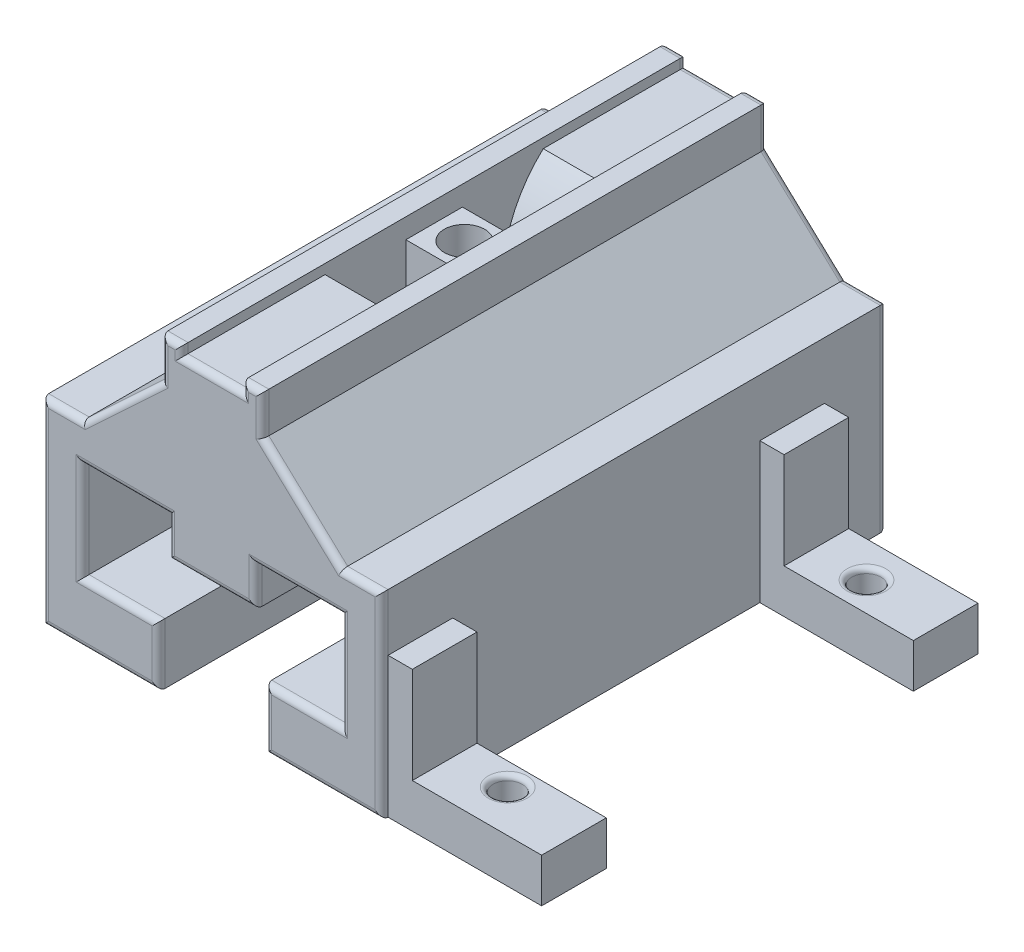
SolidWorks part; units mm, degrees
ref_plane "Front" through (0, 0, 0) normal (0, 0, 1) x (1, 0, 0)
ref_plane "Top" through (0, 0, 0) normal (0, 1, 0) x (1, 0, 0)
ref_plane "Right" through (0, 0, 0) normal (1, 0, 0) x (0, 0, -1)
sketch "Sketch2" plane through (0, 0, 0) normal (0, 0, 1) x (1, 0, 0)
  line L0 (-4.191, 2.6476) -> (-10.16, 2.6476)
  line L1 (-10.16, 2.6476) -> (-10.16, 10.3311)
  line L2 (-10.16, 10.3311) -> (-3.429, 10.3311)
  line L3 (-3.429, 10.3311) -> (-3.429, 7.2831)
  line L4 (-3.429, 7.2831) -> (3.429, 7.2831)
  line L5 (0, -13.7255) -> (0, 13.7255) construction
  line L6 (-4.191, 2.6476) -> (-4.191, -2.1149)
  line L7 (-4.191, -2.1149) -> (-13.335, -2.1149)
  line L8 (-13.335, -2.1149) -> (-13.335, 13.3791)
  line L9 (-13.335, 13.3791) -> (-10.16, 13.3791)
  line L10 (-10.16, 13.3791) -> (-3.9687, 19.1576)
  line L11 (-3.9687, 19.1576) -> (-3.9688, 22.3326)
  line L12 (-3.9688, 22.3326) -> (-2.3813, 22.3326)
  line L13 (-2.3813, 22.3326) -> (-2.3813, 21.5706)
  line L14 (-2.3813, 21.5706) -> (2.3813, 21.5706)
  line L15 (2.3813, 22.3326) -> (2.3813, 21.5706)
  line L16 (3.9688, 22.3326) -> (2.3813, 22.3326)
  line L17 (3.9687, 19.1576) -> (3.9688, 22.3326)
  line L18 (10.16, 13.3791) -> (3.9687, 19.1576)
  line L19 (13.335, 13.3791) -> (10.16, 13.3791)
  line L20 (13.335, -2.1149) -> (13.335, 13.3791)
  line L21 (4.191, -2.1149) -> (13.335, -2.1149)
  line L22 (4.191, 2.6476) -> (4.191, -2.1149)
  line L23 (3.429, 10.3311) -> (3.429, 7.2831)
  line L24 (10.16, 10.3311) -> (3.429, 10.3311)
  line L25 (10.16, 2.6476) -> (10.16, 10.3311)
  line L26 (4.191, 2.6476) -> (10.16, 2.6476)
  point P23 (0, 21.5706)
  point P32 (0, 7.2831)
  dimension "D1" = 4.7625
  dimension "D2" = 9.144
  dimension "D3" = 3.175
  dimension "D4" = 15.494
  dimension "D5" = 3.048
  dimension "D6" = 3.048
  dimension "D7" = 14.2875
  dimension "D8" = 3.175
  dimension "D9" = 0.762
  dimension "D10" = 1.5875
  dimension "D11" = 2.3813
  dimension "D12" = 3.175
  dimension "D13" = 6.731
  dimension "D14" = 3.429
extrude "Boss-Extrude1" add sketch "Sketch2" along normal blind 39.6875
sketch "Sketch3" plane through (0, 21.5706, 0) normal (0, 1, 0) x (1, 0, 0)
  line L0 (0, 0) -> (0, -39.6875) construction
  line L1 (-13.335, -19.8438) -> (13.335, -19.8438) construction
  line L2 (-13.335, -39.6875) -> (-13.335, 0) construction
  line L3 (13.335, -39.6875) -> (13.335, 0) construction
  line L4 (2.3813, 0) -> (-2.3813, 0)
  line L5 (-2.3813, 0) -> (-2.3813, -39.6875)
  line L6 (-2.3813, -39.6875) -> (2.3813, -39.6875)
  line L7 (2.3813, -39.6875) -> (2.3813, 0)
  line L8 (2.3813, 0) -> (-2.3813, 0)
  line L9 (-2.3813, 0) -> (-2.3813, -39.6875)
  line L10 (-2.3813, -39.6875) -> (2.3813, -39.6875)
  line L11 (2.3813, -39.6875) -> (2.3813, 0)
  circle A0 centre (0, -19.8437) radius 1.5875
  dimension "D2" = 3.175
  dimension "D1" = 0
extrude "Cut-Extrude1" cut sketch "Sketch3" against normal blind 39.6875 contours A0 region at (0, 21.5706, 19.8437)
sketch "Sketch4" plane through (0, 7.2831, 0) normal (0, -1, 0) x (1, 0, 0)
  line L1 (0.9165, 18.2562) -> (1.8331, 19.8437)
  line L2 (1.8331, 19.8437) -> (0.9165, 21.4312)
  line L3 (0.9165, 21.4312) -> (-0.9165, 21.4312)
  line L4 (-3.429, 0) -> (3.429, 0)
  line L5 (3.429, 0) -> (3.429, 39.6875)
  line L6 (3.429, 39.6875) -> (-3.429, 39.6875)
  line L7 (-3.429, 39.6875) -> (-3.429, 0)
  line L8 (-3.429, 0) -> (3.429, 0)
  line L9 (3.429, 0) -> (3.429, 39.6875)
  line L10 (3.429, 39.6875) -> (-3.429, 39.6875)
  line L11 (-3.429, 39.6875) -> (-3.429, 0)
  line L12 (-0.9165, 21.4312) -> (-1.8331, 19.8437)
  line L13 (-1.8331, 19.8437) -> (-0.9165, 18.2562)
  line L14 (-0.9165, 18.2562) -> (0.9165, 18.2562)
  circle A0 centre (0, 19.8437) radius 1.5875 construction
  circle M11 centre (0, 19.8437) radius 1.5875
  dimension "D2" = 3.175
  dimension "D1" = 0
extrude "Cut-Extrude3" cut sketch "Sketch4" against normal blind 5 contours M11 | L12 L13 M11 | L13 L14 M11 | L14 L1 M11 | L1 L2 M11 | L2 L3 M11 | L3 L12 M11 region at (0.8204, 7.2831, 18.4228) region at (1.6408, 7.2831, 19.8437) region at (0, 7.2831, 19.8437) region at (-0.8204, 7.2831, 18.4228) region at (-1.6408, 7.2831, 19.8437) region at (0.8204, 7.2831, 21.2647) region at (-0.8204, 7.2831, 21.2647)
sketch "Sketch5" plane through (2.3813, 0, 0) normal (-1, 0, 0) x (0, 0, 1)
  line L3 (11.2713, 21.5706) -> (17.6212, 21.5706)
  line L6 (28.4163, 21.5706) -> (22.0663, 21.5706)
  line L7 (28.1707, 7.2831) -> (20.7963, 7.2831)
  line L8 (22.0663, 10.3311) -> (17.6212, 10.3311)
  line L9 (19.8438, 21.5706) -> (19.8438, 7.2831) construction
  line L12 (11.5168, 7.2831) -> (17.6213, 7.2831)
  line L16 (20.7963, 7.2831) -> (17.6213, 7.2831)
  line L19 (22.0663, 20.7705) -> (17.6212, 20.7705)
  line L21 (17.6212, 20.7705) -> (17.6212, 10.3311)
  line L22 (22.0663, 20.7705) -> (22.0663, 10.3311)
  line L24 (17.6212, 21.5706) -> (22.0663, 21.5706)
  arc A0 (28.4163, 21.5706) -> (28.1707, 7.2831) centre (35.1321, 14.3093) ccw
  arc A1 (11.2713, 21.5706) -> (11.5168, 7.2831) centre (4.5554, 14.3093) cw
  dimension "D1" = 4.445
extrude "Cut-Extrude5" cut sketch "Sketch5" along normal up to surface (4.7625 mm away) up to face at (-2.3813, 21.9516, 19.8438)
sketch "Sketch6" plane through (-2.3813, 0, 0) normal (1, 0, 0) x (0, 0, -1)
  line L0 (-26.0766, 10.3311) -> (-13.6109, 10.3311)
  line L1 (-11.5168, 7.2831) -> (-28.1707, 7.2831)
  line L6 (0, 21.5706) -> (0, 22.3326)
  line L7 (0, 22.3326) -> (-39.6875, 22.3326)
  line L8 (-39.6875, 22.3326) -> (-39.6875, 21.5706)
  line L9 (-39.6875, 21.5706) -> (-28.4163, 21.5706)
  line L10 (-28.1707, 7.2831) -> (-11.5168, 7.2831)
  line L11 (-11.2713, 21.5706) -> (0, 21.5706)
  arc A2 (-28.1707, 7.2831) -> (-28.4163, 21.5706) centre (-35.1321, 14.3093) ccw
  arc A3 (-11.2713, 21.5706) -> (-11.5168, 7.2831) centre (-4.5554, 14.3093) ccw
  arc A4 (-28.1707, 7.2831) -> (-26.0766, 10.3311) centre (-35.1321, 14.3093) ccw
  arc A5 (-13.6109, 10.3311) -> (-11.5168, 7.2831) centre (-4.5554, 14.3093) ccw
  dimension "D1" = 0
extrude "Cut-Extrude6" cut sketch "Sketch6" against normal blind 3.175 and the other way blind 8.255 contours L1 A4 L0 A5
fillet "Fillet1" radius 0.508 52 edges at (-7.1755, 2.6476, 0) (-10.16, 6.4894, 0) (-6.7945, 10.3311, 0) (-3.429, 8.8071, 0) (0, 7.2831, 0) (3.429, 8.8071, 0) (6.7945, 10.3311, 0) (10.16, 6.4894, 0) (7.1755, 2.6476, 0) (4.191, 0.2664, 0) (8.763, -2.1149, 0) (13.335, 5.6321, 0) (11.7475, 13.3791, 0) (7.0644, 16.2684, 0) (3.9688, 20.7451, 0) (3.175, 22.3326, 0) (2.3813, 21.9516, 0) (0, 21.5706, 0) (-2.3813, 21.9516, 0) (-3.175, 22.3326, 0) (-3.9688, 20.7451, 0) (-7.0644, 16.2684, 0) (-11.7475, 13.3791, 0) (-13.335, 5.6321, 0) (-8.763, -2.1149, 0) (-4.191, 0.2664, 0) (-8.763, -2.1149, 39.6875) (-13.335, 5.6321, 39.6875) (-11.7475, 13.3791, 39.6875) (-7.0644, 16.2684, 39.6875) (-3.9688, 20.7451, 39.6875) (-3.175, 22.3326, 39.6875) (-2.3813, 21.9516, 39.6875) (0, 21.5706, 39.6875) (2.3813, 21.9516, 39.6875) (3.175, 22.3326, 39.6875) (3.9688, 20.7451, 39.6875) (7.0644, 16.2684, 39.6875) (11.7475, 13.3791, 39.6875) (13.335, 5.6321, 39.6875) (8.763, -2.1149, 39.6875) (4.191, 0.2664, 39.6875) (7.1755, 2.6476, 39.6875) (10.16, 6.4894, 39.6875) (6.7945, 10.3311, 39.6875) (3.429, 8.8071, 39.6875) (0, 7.2831, 39.6875) (-3.429, 8.8071, 39.6875) (-6.7945, 10.3311, 39.6875) (-10.16, 6.4894, 39.6875) (-7.1755, 2.6476, 39.6875) (-4.191, 0.2664, 39.6875)
sketch "Sketch7" plane through (13.335, 0, 0) normal (1, 0, 0) x (0, 0, -1)
  line L0 (-39.1795, -2.1149) -> (-0.508, -2.1149) construction
  line L1 (-39.1795, -2.1149) -> (-34.0995, -2.1149)
  line L2 (-39.1795, -2.1149) -> (-39.1795, 8.9054)
  line L3 (-39.1795, 8.9054) -> (-34.0995, 8.9054)
  line L4 (-34.0995, -2.1149) -> (-34.0995, 8.9054)
  line L5 (-9.9695, -2.1149) -> (-4.8895, -2.1149)
  line L6 (-9.9695, -2.1149) -> (-9.9695, 8.9054)
  line L7 (-9.9695, 8.9054) -> (-4.8895, 8.9054)
  line L8 (-4.8895, -2.1149) -> (-4.8895, 8.9054)
  dimension "D1" = 5.08
  dimension "D2" = 24.13
extrude "Boss-Extrude2" add sketch "Sketch7" along normal blind 1.905
sketch "Sketch8" plane through (15.24, 0, 0) normal (1, 0, 0) x (0, 0, -1)
  line L0 (-39.1795, 1.336) -> (-34.0995, 1.336)
  line L1 (-9.9695, 1.336) -> (-4.8895, 1.336)
  line L4 (-39.1795, 8.9054) -> (-39.1795, -2.1149)
  line L5 (-39.1795, -2.1149) -> (-34.0995, -2.1149)
  line L6 (-34.0995, -2.1149) -> (-34.0995, 8.9054)
  line L7 (-34.0995, 8.9054) -> (-39.1795, 8.9054)
  line L8 (-39.1795, 8.9054) -> (-39.1795, -2.1149)
  line L9 (-39.1795, -2.1149) -> (-34.0995, -2.1149)
  line L10 (-34.0995, -2.1149) -> (-34.0995, 8.9054)
  line L11 (-34.0995, 8.9054) -> (-39.1795, 8.9054)
  line L12 (-9.9695, 8.9054) -> (-9.9695, -2.1149)
  line L13 (-9.9695, -2.1149) -> (-4.8895, -2.1149)
  line L14 (-4.8895, -2.1149) -> (-4.8895, 8.9054)
  line L15 (-4.8895, 8.9054) -> (-9.9695, 8.9054)
  line L16 (-9.9695, 8.9054) -> (-9.9695, -2.1149)
  line L17 (-9.9695, -2.1149) -> (-4.8895, -2.1149)
  line L18 (-4.8895, -2.1149) -> (-4.8895, 8.9054)
  line L19 (-4.8895, 8.9054) -> (-9.9695, 8.9054)
  line M9 (-39.1795, 8.9054) -> (-39.1795, -2.1149)
  line M10 (-39.1795, -2.1149) -> (-34.0995, -2.1149)
  line M11 (-34.0995, -2.1149) -> (-34.0995, 8.9054)
  dimension "D1" = 0
  dimension "D2" = 0
extrude "Boss-Extrude3" add sketch "Sketch8" along normal blind 10.16 contours L0 M9 M10 M11 | L17 L18 L1 L16 region at (15.24, -0.3894, 36.6395) region at (15.24, -0.3894, 7.4295)
sketch "Sketch9" plane through (0, -2.1149, 0) normal (0, -1, 0) x (1, 0, 0)
  line L11 (4.191, 39.1795) -> (4.191, 0.508)
  line L12 (4.191, 0.508) -> (13.335, 0.508)
  line L13 (13.335, 0.508) -> (13.335, 4.8895)
  line L14 (13.335, 4.8895) -> (25.4, 4.8895)
  line L15 (25.4, 4.8895) -> (25.4, 9.9695)
  line L16 (25.4, 9.9695) -> (13.335, 9.9695)
  line L17 (13.335, 9.9695) -> (13.335, 34.0995)
  line L18 (13.335, 34.0995) -> (25.4, 34.0995)
  line L19 (25.4, 34.0995) -> (25.4, 39.1795)
  line L20 (25.4, 39.1795) -> (13.335, 39.1795)
  line L21 (13.335, 39.1795) -> (4.191, 39.1795)
  line L22 (4.191, 39.1795) -> (4.191, 0.508)
  line L23 (4.191, 0.508) -> (13.335, 0.508)
  line L24 (13.335, 0.508) -> (13.335, 4.8895)
  line L25 (13.335, 4.8895) -> (25.4, 4.8895)
  line L26 (25.4, 4.8895) -> (25.4, 9.9695)
  line L27 (25.4, 9.9695) -> (13.335, 9.9695)
  line L28 (13.335, 9.9695) -> (13.335, 34.0995)
  line L29 (13.335, 34.0995) -> (25.4, 34.0995)
  line L30 (25.4, 34.0995) -> (25.4, 39.1795)
  line L31 (25.4, 39.1795) -> (13.335, 39.1795)
  line L32 (13.335, 39.1795) -> (4.191, 39.1795)
  circle A0 centre (19.431, 7.6835) radius 1.143
  circle A1 centre (19.431, 35.8775) radius 1.143
  dimension "D2" = 2.286
  dimension "D4" = 2.286
  dimension "D6" = 6.096
  dimension "D7" = 6.096
  dimension "D3" = 2.286
  dimension "D5" = 1.778
  dimension "D1" = 0
extrude "Cut-Extrude7" cut sketch "Sketch9" against normal up to next contours A1 | A0 region at (19.431, -2.1149, 7.6835) region at (19.431, -2.1149, 35.8775)
fillet "Fillet2" radius 0.381 4 edges at (20.574, -2.1149, 7.6835) (20.574, -2.1149, 35.8775) (18.288, 1.336, 7.6835) (18.288, 1.336, 35.8775)
